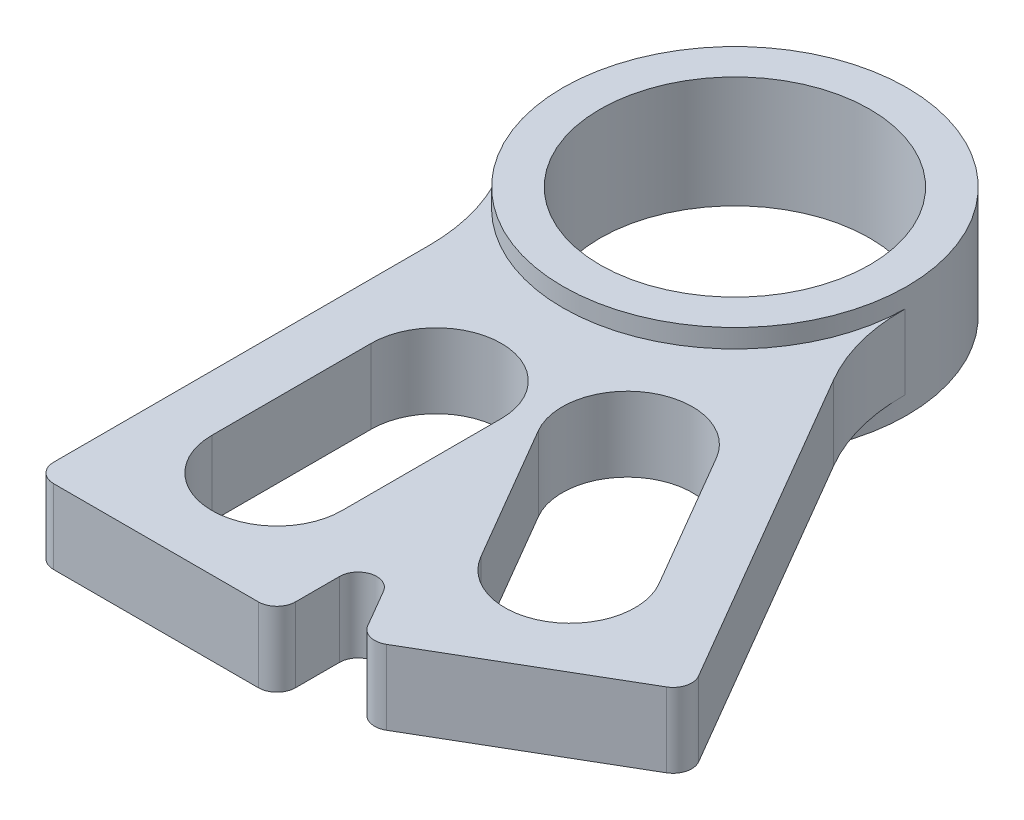
SolidWorks part; units mm, degrees
ref_plane "Front Plane" through (0, 0, 0) normal (0, 0, 1) x (1, 0, 0)
ref_plane "Top Plane" through (0, 0, 0) normal (0, 1, 0) x (1, 0, 0)
ref_plane "Right Plane" through (0, 0, 0) normal (1, 0, 0) x (0, 0, -1)
sketch "Sketch1" plane through (0, 0, 0) normal (0, 1, 0) x (1, 0, 0)
  line L0 (0, 0) -> (0, -49.3903) construction
  line L1 (0, 0) -> (24.8801, -42.666) construction
  line L2 (0, -39.0716) -> (0, -25.4826) construction
  line L3 (-5.5562, -39.0716) -> (-5.5562, -25.4826)
  line L4 (5.5563, -39.0716) -> (5.5563, -25.4826)
  line L5 (19.6821, -33.7521) -> (12.8367, -22.0132) construction
  line L6 (14.8823, -36.551) -> (8.0369, -24.8121)
  line L7 (24.4818, -30.9531) -> (17.6365, -19.2142)
  line L8 (0, -49.3903) -> (0, -44.6278) construction
  line L9 (24.8801, -42.666) -> (22.481, -38.5519) construction
  line L10 (-10.3187, -49.3903) -> (10.3188, -49.3903)
  line L11 (15.9662, -47.864) -> (33.794, -37.4679)
  line L12 (-10.3187, -49.3903) -> (-10.3187, -10.4432)
  line L13 (10.3188, -49.3903) -> (10.3188, -38.1794)
  line L14 (33.794, -37.4679) -> (14.1746, -3.8234)
  line L15 (15.9662, -47.864) -> (10.3188, -38.1794)
  line L16 (178.5686, -306.221) -> (14.7943, -25.3703) construction
  line L22 (0, 0) -> (10.3188, -38.1794) construction
  circle A0 centre (0, 0) radius 11.5062
  circle A1 centre (0, 0) radius 14.6812
  arc A2 (-5.5562, -39.0716) -> (5.5563, -39.0716) centre (0, -39.0716) ccw
  arc A3 (5.5563, -25.4826) -> (-5.5562, -25.4826) centre (0, -25.4826) ccw
  arc A4 (14.8823, -36.551) -> (24.4818, -30.9531) centre (19.6821, -33.7521) ccw
  arc A5 (17.6365, -19.2142) -> (8.0369, -24.8121) centre (12.8367, -22.0132) ccw
  point P8 (0, -32.2771)
  point P13 (16.2594, -27.8826)
  point P25 (0, -49.3903)
  point P27 (24.8801, -42.666)
  dimension "D2" = 29.3624
  dimension "D3" = 4.7625
  dimension "D4" = 4.7625
  dimension "D5" = 13.589
  dimension "D6" = 49.3903
  dimension "D7" = 20.6375
extrude "Bearing_Insert_Extrude" add sketch "Sketch1" along normal mid plane 9.525 contours A1 A0 region at (-5.4988, 0, -13.1636)
extrude "Apex_Slot_Insert_Extrude" add sketch "Sketch1<4>" along normal mid plane 6.35 contours A1 L12 L10 L13 L15 L11 L14 A5 L7 A4 L6 A3 L4 A2 L3 region at (8.1875, 0, 30.2936)
sketch "Sketch1<4>" plane through (0, 0, 0) normal (0, 1, 0) x (1, 0, 0) same geometry as "Sketch1"
fillet "Fillet1" radius 16.002 2 edges at (14.1746, 0, 3.8234) (-10.3187, 0, 10.4432)
fillet "Fillet2" radius 1.5875 5 edges at (33.794, 0, 37.4679) (15.9662, 0, 47.864) (10.3188, 0, 38.1794) (10.3188, 0, 49.3903) (-10.3187, 0, 49.3903)
equation "\"Apex_thickness\"= .25"
equation "\"Bearing_diameter\"= 0.906in"
equation "\"A-arm_angle\"= 39.1893"
equation "\"D1@Sketch1\"=\"Bearing_diameter\""
equation "\"D1@Apex_Slot_Insert_Extrude\"=\"Apex_thickness\""
